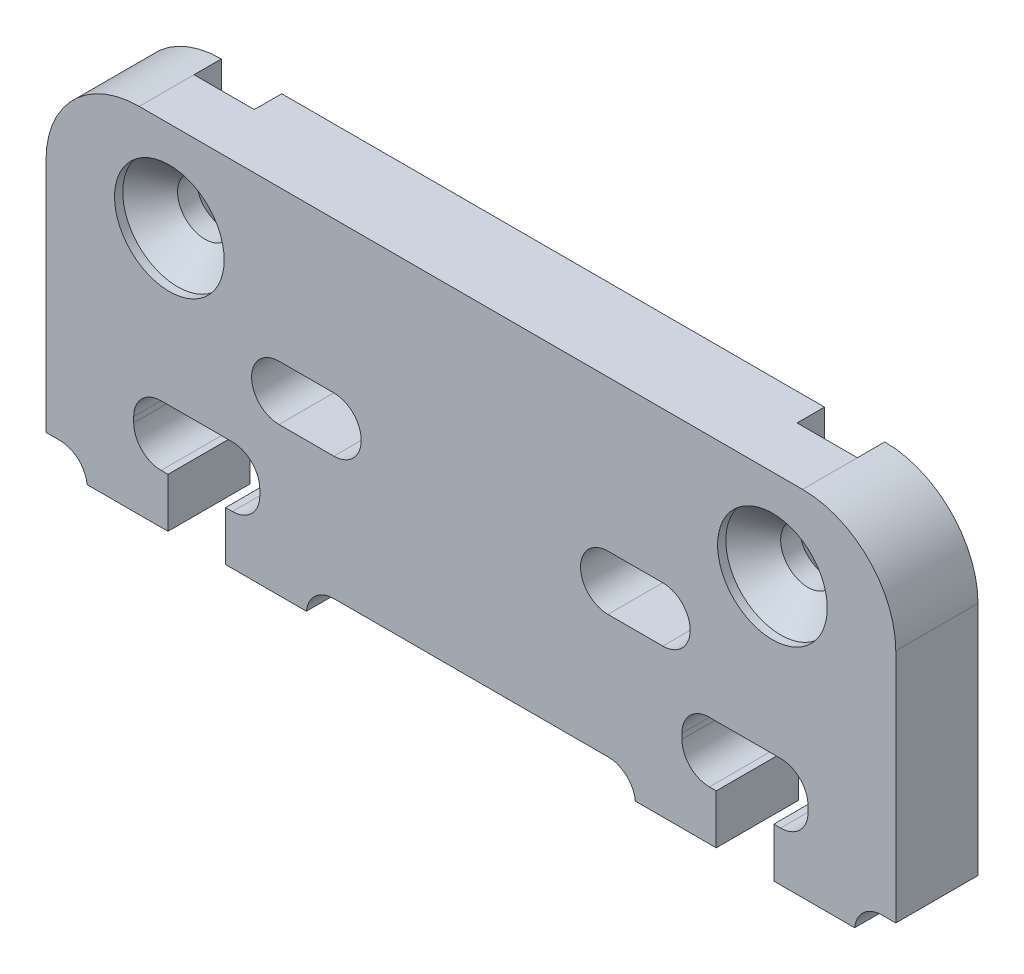
SolidWorks part; units mm, degrees
ref_plane "Front Plane" through (0, 0, 0) normal (0, 0, 1) x (1, 0, 0)
ref_plane "Top Plane" through (0, 0, 0) normal (0, 1, 0) x (1, 0, 0)
ref_plane "Right Plane" through (0, 0, 0) normal (1, 0, 0) x (0, 0, -1)
sketch "Sketch1" plane through (0, 0, 0) normal (0, 0, 1) x (1, 0, 0)
  line L0 (-10, -6.9) -> (-10, 6) construction
  line L1 (-15.5, 6) -> (15.5, 6)
  line L2 (-15.5, 6) -> (-15.5, -6)
  line L3 (-15.5, -6) -> (15.5, -6)
  line L4 (15.5, 6) -> (15.5, -6)
  line L5 (-15.5, 6) -> (15.5, -6) construction
  line L6 (-15.5, -6) -> (15.5, 6) construction
  line L7 (-15.5, -6) -> (-6, -6)
  line L9 (-14, -6.9) -> (-6, -6.9)
  line L10 (-6, -6) -> (-6, -6.9)
  line L11 (0, 6) -> (0, -6) construction
  line L12 (-11.05, -5.1) -> (-8.95, -5.1)
  line L13 (-11.05, -5.1) -> (-11.05, -6.9)
  line L14 (-11.05, -6.9) -> (-8.95, -6.9)
  line L15 (-8.95, -5.1) -> (-8.95, -6.9)
  line L16 (-11.05, -5.1) -> (-8.95, -6.9) construction
  line L17 (-11.05, -6.9) -> (-8.95, -5.1) construction
  line L18 (-12.3, -2.9) -> (-7.7, -2.9)
  line L19 (-12.3, -2.9) -> (-12.3, -5.1)
  line L20 (-12.3, -5.1) -> (-7.7, -5.1)
  line L21 (-7.7, -2.9) -> (-7.7, -5.1)
  line L22 (-12.3, -2.9) -> (-7.7, -5.1) construction
  line L23 (-12.3, -5.1) -> (-7.7, -2.9) construction
  line L24 (12.3, -2.9) -> (7.7, -2.9)
  line L25 (12.3, -2.9) -> (12.3, -5.1)
  line L26 (12.3, -5.1) -> (7.7, -5.1)
  line L27 (7.7, -2.9) -> (7.7, -5.1)
  line L28 (11.05, -5.1) -> (8.95, -5.1)
  line L29 (11.05, -5.1) -> (11.05, -6.9)
  line L30 (11.05, -6.9) -> (8.95, -6.9)
  line L31 (8.95, -5.1) -> (8.95, -6.9)
  line L32 (15.5, -6) -> (6, -6)
  line L33 (6, -6) -> (6, -6.9)
  line L34 (14, -6.9) -> (6, -6.9)
  line L36 (-14, -6.9) -> (-14, -6)
  line L37 (14, -6.9) -> (14, -6)
  line L38 (10, -2.9) -> (10, -6.9) construction
  line L39 (7, -0.5) -> (5, -0.5) construction
  line L40 (7, -1.5) -> (5, -1.5)
  line L41 (7, 0.5) -> (5, 0.5)
  line L42 (-7, -0.5) -> (-5, -0.5) construction
  line L43 (-7, -1.5) -> (-5, -1.5)
  line L44 (-7, 0.5) -> (-5, 0.5)
  arc A0 (7, -1.5) -> (7, 0.5) centre (7, -0.5) ccw
  arc A1 (5, 0.5) -> (5, -1.5) centre (5, -0.5) ccw
  arc A2 (-7, -1.5) -> (-7, 0.5) centre (-7, -0.5) cw
  arc A3 (-5, 0.5) -> (-5, -1.5) centre (-5, -0.5) cw
  point P0 (0, 0)
  point P11 (-10, -6)
  point P16 (-10, -4)
  point P40 (6, -0.5)
  point P47 (-6, -0.5)
  dimension "D1" = 31
  dimension "D2" = 12
  dimension "D3" = 0.9
  dimension "D4" = 8
  dimension "D5" = 2.1
  dimension "D6" = 1.8
  dimension "D7" = 2.2
  dimension "D8" = 4.6
  dimension "D9" = 20
  dimension "D10" = 2
  dimension "D11" = 2
  dimension "D12" = 12
  dimension "D13" = 5.5
extrude "Base shape" add sketch "Sketch1" along normal blind 3 contours L31 L26 L27 L24 L25 L29 L3 L4 L1 L2 L13 L20 L19 L18 L21 L15 | L3 L15 L9 L10 | L13 L3 L9 | L34 L31 L3 L33 | L3 L29 L34 region at (0, 0.3269, 0) region at (-12.525, -6.45, 0) region at (12.525, -6.45, 0) region at (-7.475, -6.45, 0) region at (7.475, -6.45, 0)
fillet "Edge radiuses" radius 3.4 2 edges at (15.5, 6, 1.5) (-15.5, 6, 1.5)
sketch "Sketch2" plane through (0, 0, 0) normal (0, 0, -1) x (-1, 0, 0)
  line L0 (0, 6) -> (0, -6) construction
  line L10 (12.1, 6) -> (-12.1, 6) construction
  line L11 (6, -6) -> (-6, -6) construction
  line L16 (-14, -6) -> (-15.5, -6) construction
  line L17 (-12.1, 6.1) -> (-9.9, 6.1)
  line L18 (-12.1, 6.1) -> (-12.1, 0.3)
  line L19 (-11.1, -0.7) -> (-10.9, -0.7)
  line L20 (-9.9, 6.1) -> (-9.9, 0.3)
  line L21 (-12.1, 6.1) -> (-9.9, -0.7) construction
  line L22 (-12.1, -0.7) -> (-9.9, 6.1) construction
  line L23 (12.1, 6.1) -> (9.9, 6.1)
  line L24 (12.1, 6.1) -> (12.1, 0.3)
  line L25 (11.1, -0.7) -> (10.9, -0.7)
  line L26 (9.9, 6.1) -> (9.9, 0.3)
  arc A8 (-10.9, -0.7) -> (-9.9, 0.3) centre (-10.9, 0.3) ccw
  arc A9 (-12.1, 0.3) -> (-11.1, -0.7) centre (-11.1, 0.3) ccw
  arc A10 (12.1, 0.3) -> (11.1, -0.7) centre (11.1, 0.3) cw
  arc A11 (10.9, -0.7) -> (9.9, 0.3) centre (10.9, 0.3) cw
  point P6 (-11, 2.7)
  dimension "D5" = 1
  dimension "D1" = 6.8
  dimension "D2" = 2.2
  dimension "D3" = 22
  dimension "D4" = 8.7
extrude "Camera mount pockets" cut sketch "Sketch2" against normal blind 1
sketch "Sketch3" plane through (0, 0, 1) normal (0, 0, -1) x (-1, 0, 0)
  line L3 (0, 6) -> (0, -6) construction
  line L5 (6, -6) -> (-6, -6) construction
  line L6 (-11.1, -0.7) -> (-10.9, -0.7) construction
  line L7 (-12.1, 6.1) -> (-9.9, 6.1)
  line L8 (-12.1, 6.1) -> (-12.1, -0.7)
  line L9 (-12.1, -0.7) -> (-9.9, -0.7)
  line L10 (-9.9, 6.1) -> (-9.9, -0.7)
  line L11 (-12.1, 6.1) -> (-9.9, -0.7) construction
  line L12 (-12.1, -0.7) -> (-9.9, 6.1) construction
  line L13 (-12.1, 6) -> (-12.1, 0.3) construction
  circle A0 centre (-11, 2.7) radius 1
  circle A1 centre (11, 2.7) radius 1
  point P2 (-11, 2.7)
  point P17 (-11, -0.7)
  point P18 (-11, -0.7)
  dimension "D1" = 2
  dimension "D2" = 6.8
extrude "Camera mount holes" cut sketch "Sketch3" against normal up to next contours A0 | A1 region at (11, 2.7, 1) region at (-11, 2.7, 1)
hole_wizard "CSK for M2 Flat Head Machine Screw1" positions "Sketch4" profile "Sketch5" countersink size "M2" standard "ANSI Metric" end condition through all
sketch "Sketch4" plane through (0, 0, 3) normal (0, 0, 1) x (1, 0, 0)
  point P0 (-11, 2.7)
  point P3 (11, 2.7)
sketch "Sketch5" plane through (-11, 2.7, 3) normal (1, 0, 0) x (0, -1, 0)
  line L0 (0, 0) -> (0, 3)
  line L1 (0, 3) -> (1, 3)
  line L2 (1, 3) -> (1, 1.3)
  line L3 (1, 1.3) -> (2, 0.3)
  line L4 (2, 0.3) -> (2, 0)
  line L6 (2, 0) -> (0, 0)
  line L7 (-1, 1.3) -> (-2, 0.3) construction
  line L11 (0, -6.35) -> (0, 107.95) construction
  dimension "Thru Hole Dia." = 2
  dimension "Thru Hole Depth" = 3
  dimension "C'Sink Dia." = 4
  dimension "C'Sink Angle" = 90
  dimension "Head Clearance" = 0.3
fillet "1mm milling radiuses" radius 1 12 edges at (-7.7, -2.9, 1.5) (-7.7, -5.1, 1.5) (12.3, -5.1, 1.5) (12.3, -2.9, 1.5) (7.7, -2.9, 1.5) (7.7, -5.1, 1.5) (-12.3, -5.1, 1.5) (-12.3, -2.9, 1.5) (14, -6, 1.5) (6, -6, 1.5) (-14, -6, 1.5) (-6, -6, 1.5)
sketch "Slot sketch" plane through (0, 0, 1) normal (0, 0, -1) x (-1, 0, 0)
  line L0 (0, 6) -> (0, -6) construction
  line L3 (-12.1, 7.2) -> (-9.9, 7.2)
  line L4 (-12.1, 6) -> (-12.1, 0.3)
  line L5 (-11.1, -0.7) -> (-10.9, -0.7)
  line L6 (-9.9, 0.3) -> (-9.9, 6)
  line L7 (-9.9, 6) -> (-12.1, 6)
  line L9 (-11.1, -0.7) -> (-10.9, -0.7)
  line L12 (9.9, 6) -> (-9.9, 6) construction
  line L25 (-12.1, 0.3) -> (-12.1, 7.2)
  line L26 (-9.9, 0.3) -> (-9.9, 7.2)
  line L27 (11.1, -0.7) -> (10.9, -0.7)
  line L28 (12.1, 0.3) -> (12.1, 7.2)
  line L29 (12.1, 7.2) -> (9.9, 7.2)
  line L30 (9.9, 0.3) -> (9.9, 7.2)
  line L31 (5.005, -6) -> (-5.005, -6) construction
  arc A2 (-12.1, 0.3) -> (-11.1, -0.7) centre (-11.1, 0.3) ccw
  arc A3 (-10.9, -0.7) -> (-9.9, 0.3) centre (-10.9, 0.3) ccw
  arc A4 (-12.1, 0.3) -> (-11.1, -0.7) centre (-11.1, 0.3) ccw
  arc A5 (-10.9, -0.7) -> (-9.9, 0.3) centre (-10.9, 0.3) ccw
  arc A6 (10.9, -0.7) -> (9.9, 0.3) centre (10.9, 0.3) cw
  arc A7 (12.1, 0.3) -> (11.1, -0.7) centre (11.1, 0.3) cw
  dimension "D3" = 1.2
  dimension "D1" = 0
sketch "Sketch8" plane through (0, 0, 0) normal (0, 0, -1) x (-1, 0, 0)
  line L0 (-14, -6) -> (14, -6) construction
  line L1 (-14, -6) -> (-2, 6) construction
  line L2 (9.9, 6) -> (-9.9, 6) construction
  line L3 (0, 6) -> (0, -6) construction
  line L4 (-11.05, -6.9) -> (-8.95, -6.9) construction
  line L5 (-10, -6.9) -> (-10, -2.9) construction
  line L6 (-11.3, -2.9) -> (-8.7, -2.9) construction
  line L7 (-15.5, -6) -> (-14, -6) construction
  line L8 (-14, -6) -> (-14, -6.9) construction
  circle A0 centre (-14.7071, -6.7071) radius 1
  circle A1 centre (14.7071, -6.7071) radius 1
  circle A2 centre (-5.2929, -6.7071) radius 1
  circle A3 centre (5.2929, -6.7071) radius 1
  dimension "D2" = 2
  dimension "D1" = 45
extrude "Square cuts" [suppressed] cut sketch "Sketch8" against normal up to next
